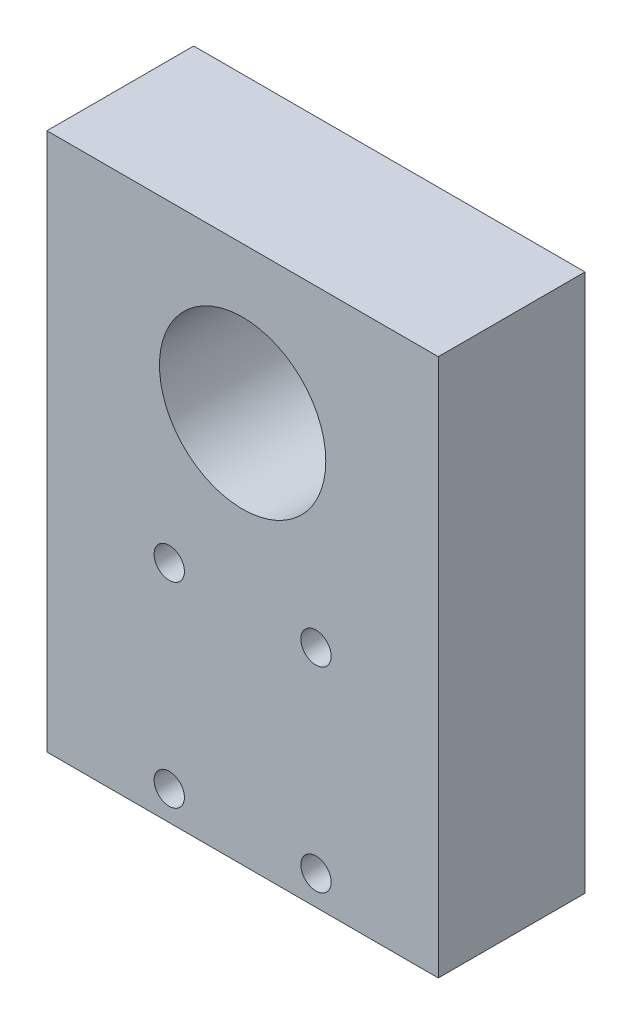
SolidWorks part; units mm, degrees
ref_plane "Front" through (0, 0, 0) normal (0, 0, 1) x (1, 0, 0)
ref_plane "Top" through (0, 0, 0) normal (0, 1, 0) x (1, 0, 0)
ref_plane "Right" through (0, 0, 0) normal (1, 0, 0) x (0, 0, -1)
sketch "Esquisse1" plane through (0, 0, 0) normal (0, 0, 1) x (1, 0, 0)
  line L1 (0, 0) -> (40, 0)
  line L2 (0, 0) -> (0, 30)
  line L3 (0, 30) -> (40, 30)
  line L4 (40, 0) -> (40, 30)
  dimension "D1" = 40
  dimension "D2" = 30
extrude "Boss.-Extru.1" add sketch "Esquisse1" along normal blind 15
sketch "Esquisse2" plane through (0, 0, 15) normal (0, 0, 1) x (1, 0, 0)
  line L0 (20, 15) -> (20, 0) construction
  line L1 (0, 0) -> (40, 0) construction
  line L2 (0, 15) -> (20, 15) construction
  line L3 (0, 30) -> (0, 0) construction
  circle A0 centre (20, 15) radius 8.5
  dimension "D1" = 17
extrude "Enlèv. mat.-Extru.1" cut sketch "Esquisse2" against normal up to vertex (15 mm away) up to point (40, 30, 0)
sketch "Esquisse3" plane through (0, 0, 15) normal (0, 0, 1) x (1, 0, 0)
  line L0 (40, 0) -> (40, 30) construction
  line L1 (0, 0) -> (40, 0)
  line L2 (0, 0) -> (0, -25)
  line L3 (0, -25) -> (40, -25)
  line L4 (40, 0) -> (40, -25)
  dimension "D1" = 25
extrude "Boss.-Extru.2" add sketch "Esquisse3" against normal up to vertex (15 mm away) up to point (40, 0, 0)
sketch "Esquisse4" plane through (0, 0, 15) normal (0, 0, 1) x (1, 0, 0)
  line L0 (20, -25) -> (20, 1) construction
  line L1 (0, -25) -> (40, -25) construction
  line L2 (20, -12) -> (30.0882, -12) construction
  circle A0 centre (27.5, -22) radius 1.55
  circle A1 centre (27.5, -2) radius 1.55
  circle A2 centre (12.5, -2) radius 1.55
  circle A3 centre (12.5, -22) radius 1.55
  dimension "D1" = 20
  dimension "D2" = 15
  dimension "D3" = 3.1
  dimension "D4" = 26
extrude "Enlèv. mat.-Extru.2" cut sketch "Esquisse4" against normal up to vertex (15 mm away) up to point (40, 30, 0)
